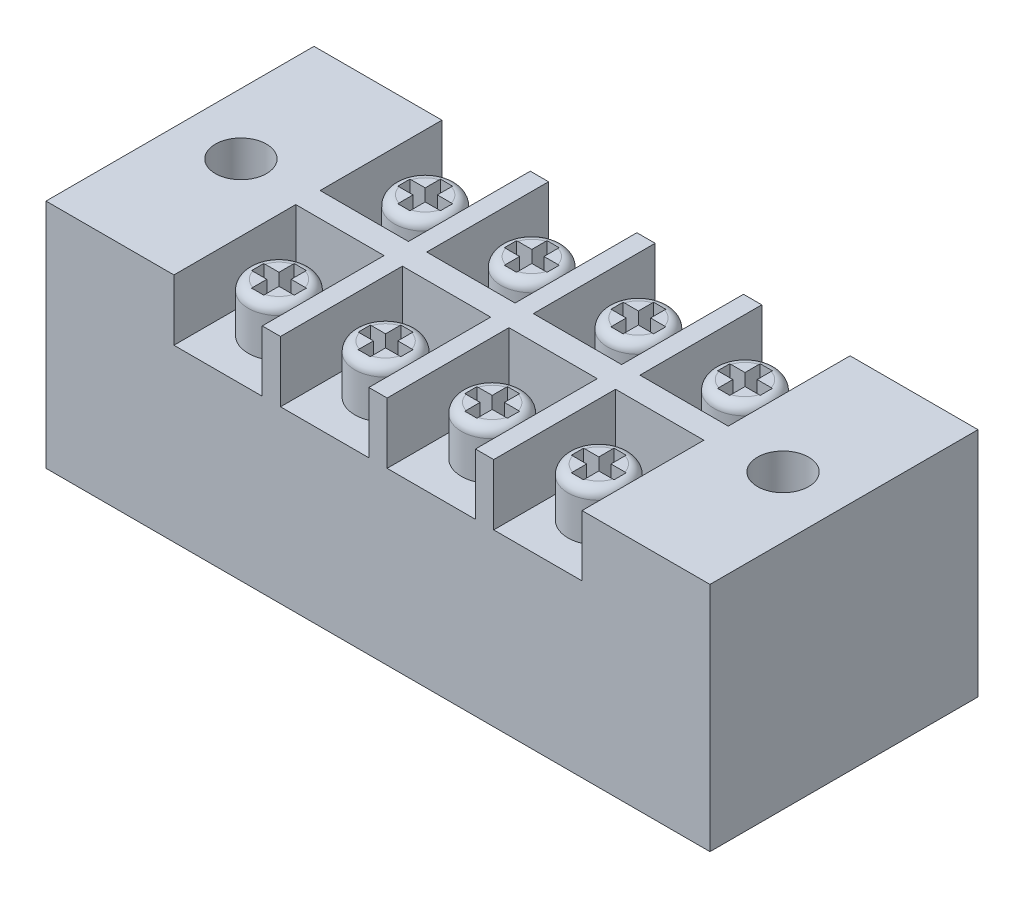
SolidWorks part; units mm, degrees
ref_plane "前视基准面" through (0, 0, 0) normal (0, 0, 1) x (1, 0, 0)
ref_plane "上视基准面" through (0, 0, 0) normal (0, 1, 0) x (1, 0, 0)
ref_plane "右视基准面" through (0, 0, 0) normal (1, 0, 0) x (0, 0, -1)
sketch "草图1" plane through (0, 0, 0) normal (0, 1, 0) x (1, 0, 0)
  line L1 (27.25, -11) -> (-27.25, -11)
  line L2 (27.25, -11) -> (27.25, 11)
  line L3 (27.25, 11) -> (-27.25, 11)
  line L4 (-27.25, -11) -> (-27.25, 11)
  line L5 (27.25, -11) -> (-27.25, 11) construction
  line L6 (27.25, 11) -> (-27.25, -11) construction
  point P0 (0, 0)
  dimension "D1" = 54.5
  dimension "D2" = 22
extrude "凸台-拉伸1" add sketch "草图1" along normal blind 19 contours L3 L4 L1 L2
sketch "草图2" plane through (0, 19, 0) normal (0, 1, 0) x (1, 0, 0)
  line L0 (0, 0) -> (0, 8.3631) construction
  circle A0 centre (-22.25, 0) radius 2.1
  circle A1 centre (22.25, 0) radius 2.1
  dimension "D1" = 4.2
  dimension "D2" = 22.25
extrude "切除-拉伸1" cut sketch "草图2" against normal through all
sketch "草图3" plane through (0, 19, 0) normal (0, 1, 0) x (1, 0, 0)
  line L0 (27.25, 11) -> (-27.25, 11) construction
  line L1 (-16.75, 11) -> (-9.5, 11)
  line L2 (-16.75, 11) -> (-16.75, 1)
  line L3 (-16.75, 1) -> (-9.5, 1)
  line L4 (-9.5, 11) -> (-9.5, 1)
  line L5 (0, 0) -> (0, 16.9944) construction
  line L6 (-8, 11) -> (-0.75, 11)
  line L7 (-8, 11) -> (-8, 1)
  line L8 (-8, 1) -> (-0.75, 1)
  line L9 (-0.75, 11) -> (-0.75, 1)
  line L10 (9.5, 11) -> (16.75, 11)
  line L11 (9.5, 11) -> (9.5, 1)
  line L12 (9.5, 1) -> (16.75, 1)
  line L13 (16.75, 11) -> (16.75, 1)
  line L14 (0, 0) -> (33.7118, 0) construction
  line L15 (16.75, -11) -> (16.75, -1)
  line L16 (9.5, -1) -> (16.75, -1)
  line L17 (9.5, -11) -> (9.5, -1)
  line L18 (9.5, -11) -> (16.75, -11)
  line L19 (-0.75, -11) -> (-0.75, -1)
  line L20 (-8, -1) -> (-0.75, -1)
  line L21 (-8, -11) -> (-8, -1)
  line L22 (-8, -11) -> (-0.75, -11)
  line L23 (-9.5, -11) -> (-9.5, -1)
  line L24 (-16.75, -1) -> (-9.5, -1)
  line L25 (-16.75, -11) -> (-16.75, -1)
  line L26 (-16.75, -11) -> (-9.5, -11)
  line L27 (8, -11) -> (0.75, -11)
  line L28 (8, -11) -> (8, -1)
  line L29 (0.75, -11) -> (0.75, -1)
  line L30 (8, -1) -> (0.75, -1)
  line L31 (0.75, 11) -> (0.75, 1)
  line L32 (8, 1) -> (0.75, 1)
  line L33 (8, 11) -> (8, 1)
  line L34 (8, 11) -> (0.75, 11)
  dimension "D1" = 7.25
  dimension "D2" = 7.25
  dimension "D3" = 1.5
  dimension "D4" = 1
  dimension "D5" = 1.5
extrude "切除-拉伸2" cut sketch "草图3" against normal blind 5
sketch "草图4" plane through (0, 14, 0) normal (0, 1, 0) x (1, 0, 0)
  line L0 (-13.125, 11) -> (-13.125, 1) construction
  line L1 (-9.5, 11) -> (-16.75, 11) construction
  line L2 (-16.75, 1) -> (-9.5, 1) construction
  line L3 (-13.2679, 6.5) -> (-12.9821, 6.5) construction
  line L4 (-13.625, 4.25) -> (-12.625, 4.25)
  line L5 (-13.625, 4.25) -> (-13.625, 5.5)
  line L6 (-13.625, 7.75) -> (-12.625, 7.75)
  line L7 (-12.625, 4.25) -> (-12.625, 5.5)
  line L8 (-13.625, 4.25) -> (-12.625, 7.75) construction
  line L9 (-13.625, 7.75) -> (-12.625, 4.25) construction
  line L10 (-14.875, 6.5) -> (-13.625, 6.5)
  line L11 (-14.875, 6.5) -> (-14.875, 5.5)
  line L12 (-14.875, 5.5) -> (-13.625, 5.5)
  line L13 (-11.375, 6.5) -> (-11.375, 5.5)
  line L14 (-14.875, 6.5) -> (-11.375, 5.5) construction
  line L15 (-14.875, 5.5) -> (-11.375, 6.5) construction
  line L16 (-13.625, 6.5) -> (-13.625, 7.75)
  line L17 (-13.625, 5.8571) -> (-13.625, 6.1429) construction
  line L18 (-13.2679, 5.5) -> (-12.9821, 5.5) construction
  line L19 (-12.625, 5.8571) -> (-12.625, 6.1429) construction
  line L20 (-12.625, 5.5) -> (-11.375, 5.5)
  line L21 (-12.625, 6.5) -> (-12.625, 7.75)
  line L22 (-12.625, 6.5) -> (-11.375, 6.5)
  circle A0 centre (-13.125, 6) radius 2.5247
  dimension "D1" = 5.0493
  dimension "D4" = 1
  dimension "D5" = 1
  dimension "D6" = 3.5
  dimension "D7" = 3.5
extrude "凸台-拉伸2" add sketch "草图4" along normal blind 4
fillet "圆角1" radius 0.8 1 edges at (-13.125, 18, -3.4753)
pattern_linear "阵列(线性)1" count 4 spacing 8.75 along (1, 0, 0) count 2 spacing 12 along (0, 0, 1) of "圆角1", "凸台-拉伸2"
